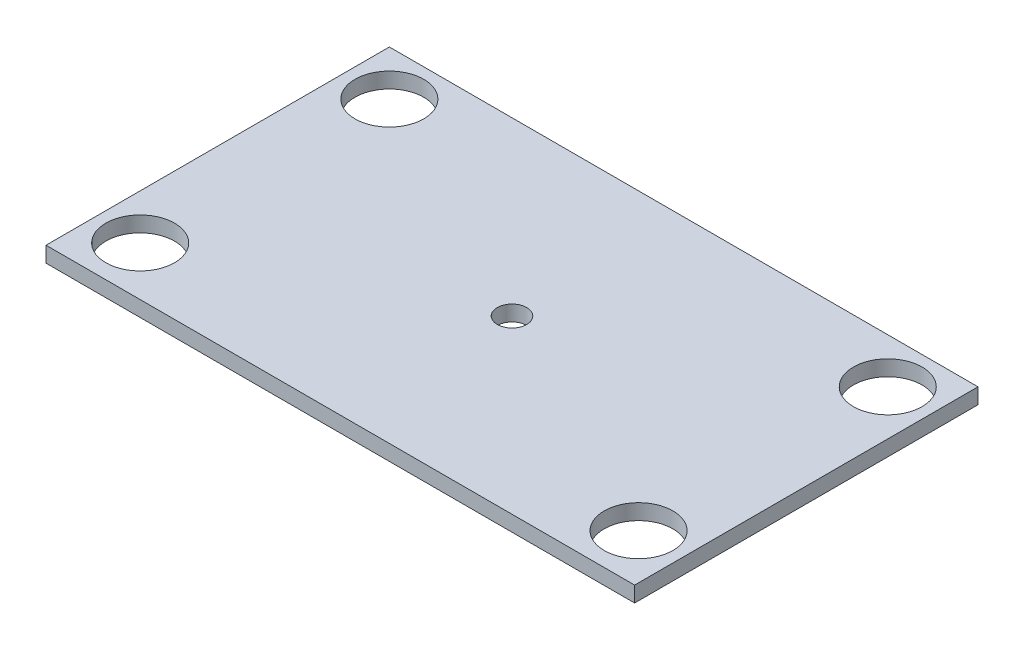
SolidWorks part; units mm, degrees
ref_plane "Front Plane" through (0, 0, 0) normal (0, 0, 1) x (1, 0, 0)
ref_plane "Top Plane" through (0, 0, 0) normal (0, 1, 0) x (1, 0, 0)
ref_plane "Right Plane" through (0, 0, 0) normal (1, 0, 0) x (0, 0, -1)
sketch "Sketch1" plane through (0, 0, 0) normal (0, 1, 0) x (1, 0, 0)
  line L0 (4.6, 30.4) -> (0, 30.4) construction
  line L1 (0, 0) -> (60, 0)
  line L2 (0, 0) -> (0, 35)
  line L3 (0, 35) -> (60, 35)
  line L4 (60, 0) -> (60, 35)
  line L5 (4.6, 30.4) -> (55.4, 30.4) construction
  line L6 (4.6, 30.4) -> (4.6, 5) construction
  line L7 (4.6, 5) -> (55.4, 5) construction
  line L8 (55.4, 30.4) -> (55.4, 5) construction
  line L9 (4.6, 30.4) -> (4.6, 35) construction
  circle A0 centre (4.6, 30.4) radius 3.5
  circle A1 centre (55.4, 30.4) radius 3.5
  circle A2 centre (4.6, 5) radius 3.5
  circle A3 centre (55.4, 5) radius 3.5
  circle A4 centre (30, 17.5) radius 1.5
  point P13 (30, 30.4)
  point P14 (30, 35)
  point P20 (60, 17.5)
  dimension "D5" = 7
  dimension "D6" = 3
  dimension "D1" = 60
  dimension "D2" = 35
  dimension "D3" = 50.8
  dimension "D4" = 25.4
extrude "Boss-Extrude1" add sketch "Sketch1" along normal blind 1.5875
